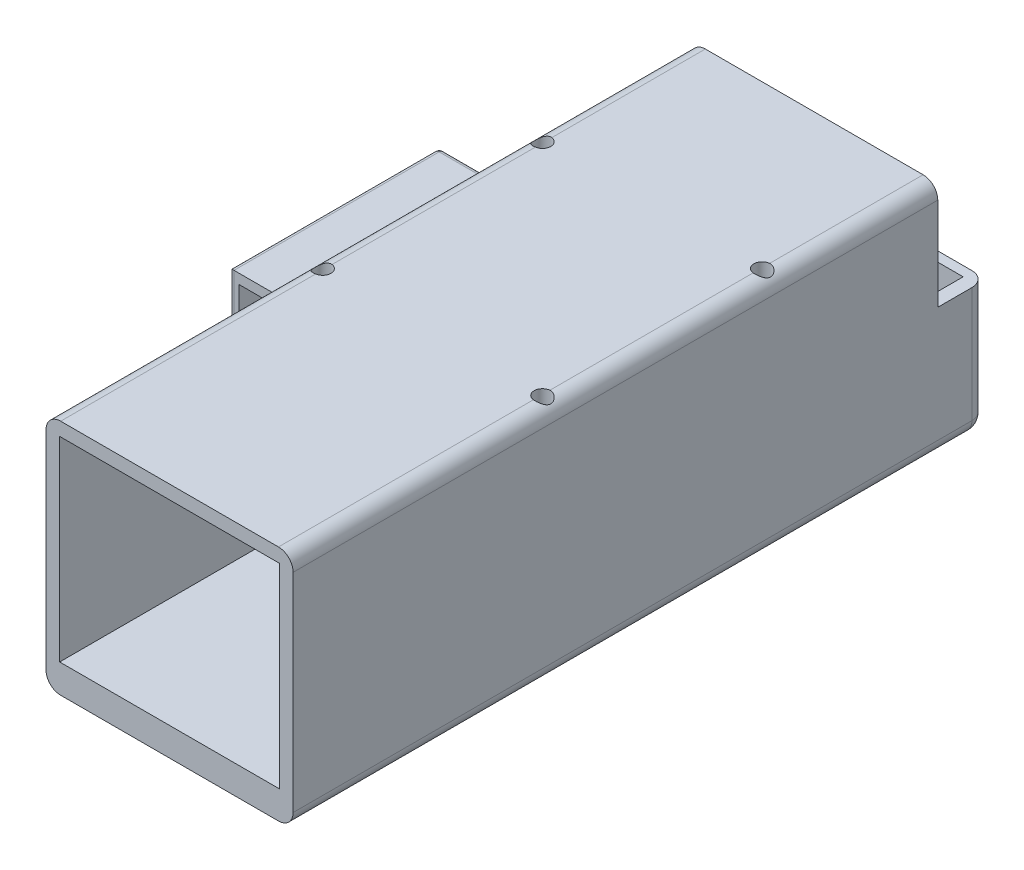
SolidWorks part; units mm, degrees
material "ABS"
ref_plane "Front Plane" through (0, 0, 0) normal (0, 0, 1) x (1, 0, 0)
ref_plane "Top Plane" through (0, 0, 0) normal (0, 1, 0) x (1, 0, 0)
ref_plane "Right Plane" through (0, 0, 0) normal (1, 0, 0) x (0, 0, -1)
sketch "Sketch1" plane through (0, 0, 0) normal (0, 0, 1) x (1, 0, 0)
  line L0 (-22.5, 20) -> (22.5, -20) construction
  line L1 (-22.5, 20) -> (22.5, 20)
  line L2 (-22.5, 20) -> (-22.5, -20)
  line L3 (-22.5, -20) -> (22.5, -20)
  line L4 (22.5, 20) -> (22.5, -20)
  line L5 (-25.3, 22.8) -> (-25.3, -22.8)
  line L6 (-25.3, -22.8) -> (25.3, -22.8)
  line L7 (25.3, 22.8) -> (25.3, -22.8)
  line L8 (-25.3, 22.8) -> (25.3, 22.8)
  point P4 (0, 0)
  dimension "D1" = 45
  dimension "D2" = 40
  dimension "D3" = 2.8
extrude "Boss-Extrude1" add sketch "Sketch1" along normal mid plane 140
sketch "Sketch2" plane through (0, 0, -70) normal (0, 0, -1) x (-1, 0, 0)
  line L1 (-25.3, 22.8) -> (25.3, 22.8)
  line L2 (-25.3, 22.8) -> (-25.3, -22.8)
  line L3 (-25.3, -22.8) -> (25.3, -22.8)
  line L4 (25.3, 22.8) -> (25.3, -22.8)
extrude "Boss-Extrude2" add sketch "Sketch2" along normal blind 2
sketch "Sketch4" plane through (0, 22.8, 0) normal (0, 1, 0) x (1, 0, 0)
  circle A0 centre (-22.5344, 28.8905) radius 1.7
  circle A1 centre (22.4656, 28.8905) radius 1.7
  circle A2 centre (22.4656, -16.1095) radius 1.7
  circle A3 centre (-22.5344, -16.1095) radius 1.7
  dimension "D1" = 3.4
  dimension "D2" = 3.4
  dimension "D3" = 3.4
  dimension "D4" = 3.4
extrude "Cut-Extrude1" cut sketch "Sketch4" against normal blind 71.5
ref_plane "Plane1" through (0, -10, 0) normal (0, 1, 0) x (1, 0, 0)
sketch "Sketch5" plane through (0, -10, 0) normal (0, 1, 0) x (1, 0, 0)
  circle A0 centre (22.4656, 28.8905) radius 2.75
  circle A1 centre (22.4656, -16.1095) radius 2.75
  circle A2 centre (-22.5344, 28.8905) radius 2.75
  circle A3 centre (-22.5344, -16.1095) radius 2.75
  dimension "D1" = 5.5
extrude "Cut-Extrude2" cut sketch "Sketch5" against normal blind 12.5
sketch "Sketch6" plane through (0, 0, 70) normal (0, 0, 1) x (1, 0, 0)
  line L10 (-25.3, -25.8) -> (25.3, -25.8)
  line L11 (25.3, -25.8) -> (25.3, -21.5065)
  line L12 (25.3, -22.8) -> (25.3, 22.8) construction
  line L13 (25.3, -21.5065) -> (-25.3, -21.5065)
  line L14 (-25.3, 22.8) -> (-25.3, -22.8) construction
  line L15 (-25.3, -21.5065) -> (-25.3, -25.8)
extrude "Boss-Extrude3" add sketch "Sketch6" against normal up to surface (142 mm away) up to face at (0, 0, -72)
sketch "Sketch7" plane through (0, -21.5065, 0) normal (0, 1, 0) x (1, 0, 0)
  circle A0 centre (-22.5344, 28.8905) radius 1.7
  circle A1 centre (22.4656, 28.8905) radius 1.7
  circle A2 centre (22.4656, -16.1095) radius 1.7
  circle A3 centre (-22.5344, -16.1095) radius 1.7
extrude "Cut-Extrude3" cut sketch "Sketch7" against normal blind 7.5
fillet "Fillet1" radius 3 8 edges at (0, -25.8, -72) (25.3, -1.5, -72) (-25.3, -1.5, -72) (0, 22.8, -72) (25.3, -25.8, -1) (-25.3, -25.8, -1) (25.3, 22.8, -1) (-25.3, 22.8, -1)
sketch "Sketch8" plane through (0, 22.8, 0) normal (0, -1, 0) x (1, 0, 0)
  line L0 (-22.3, -72) -> (-34.1108, -72) construction
  line L1 (-34.1108, -72) -> (-34.1108, -62) construction
  line L2 (-25.3, -62) -> (25.3, -62)
  line L3 (-25.3, -69) -> (-25.3, 70) construction
  line L4 (25.3, 70) -> (25.3, -69) construction
  line L5 (25.3, -62) -> (25.3, -72)
  line L6 (25.3, -72) -> (25.3, -74.9895)
  line L7 (25.3, -74.9895) -> (-25.3, -74.9895)
  line L8 (-25.3, -74.9895) -> (-25.3, -62)
  dimension "D1" = 10
extrude "Cut-Extrude4" cut sketch "Sketch8" along normal blind 22
sketch "Sketch9" plane through (-25.3, 0, 0) normal (-1, 0, 0) x (0, 0, 1)
  line L1 (-25, 11.3) -> (16, 11.3)
  line L2 (-25, 11.3) -> (-25, -13.4)
  line L3 (-25, -13.4) -> (16, -13.4)
  line L5 (-27.2067, 22.8) -> (14.4258, 22.8) construction
  line L6 (-27, 13.3) -> (-27, -15.4)
  line L7 (-27, -15.4) -> (16, -15.4)
  line L9 (-27, 13.3) -> (16, 13.3)
  line L10 (16, 13.3) -> (16, 11.3)
  line L11 (-27, 13.3) -> (18, 13.3) construction
  line L12 (18, 13.3) -> (18, -15.4) construction
  line L13 (-27, -15.4) -> (18, -15.4) construction
  line L14 (16, 11.3) -> (16, -13.4) construction
  line L15 (16, -13.4) -> (16, -15.4)
  dimension "D1" = 41
  dimension "D2" = 24.7
  dimension "D4" = 11.5
  dimension "D5" = 2
extrude "Boss-Extrude4" add sketch "Sketch9" along normal blind 14.5
sketch "Sketch10" plane through (-39.8, 0, 0) normal (-1, 0, 0) x (0, 0, 1)
  line L1 (-27, 13.3) -> (16, 13.3)
  line L2 (-27, 13.3) -> (-27, -15.4)
  line L3 (-27, -15.4) -> (16, -15.4)
  line L4 (16, 13.3) -> (16, -15.4)
extrude "Boss-Extrude5" add sketch "Sketch10" along normal blind 2
sketch "Sketch11" plane through (-41.8, 0, 0) normal (-1, 0, 0) x (0, 0, 1)
  line L0 (16, -1.05) -> (4, -1.05) construction
  line L1 (16, -15.4) -> (16, 13.3) construction
  line L2 (4, 11.3) -> (4, -13.4)
  line L6 (-10, -13.4) -> (-10, 11.3)
  line L9 (-10, 11.3) -> (4, 11.3)
  line L10 (-10, -13.4) -> (4, -13.4)
  dimension "D1" = 12
  dimension "D2" = 14
extrude "Cut-Extrude5" cut sketch "Sketch11" against normal blind 2
sketch "Sketch12" plane through (0, 0, -27) normal (0, 0, -1) x (-1, 0, 0)
  line L0 (33.55, 13.3) -> (33.55, -1.05) construction
  line L1 (41.8, 13.3) -> (25.3, 13.3) construction
  line L3 (33.55, -1.05) -> (41.8, -1.05) construction
  line L4 (41.8, 13.3) -> (41.8, -15.4) construction
  line L5 (33.55, -1.05) -> (33.55, -15.4) construction
  line L6 (41.8, -15.4) -> (25.3, -15.4) construction
  line L8 (30.55, 9.125) -> (36.55, 9.125)
  line L9 (30.55, 9.125) -> (30.55, 3.125)
  line L10 (30.55, 3.125) -> (36.55, 3.125)
  line L11 (36.55, 9.125) -> (36.55, 3.125)
  line L12 (30.55, 9.125) -> (36.55, 3.125) construction
  line L13 (30.55, 3.125) -> (36.55, 9.125) construction
  line L14 (30.55, -5.225) -> (36.55, -5.225)
  line L15 (30.55, -5.225) -> (30.55, -11.225)
  line L16 (30.55, -11.225) -> (36.55, -11.225)
  line L17 (36.55, -5.225) -> (36.55, -11.225)
  line L18 (30.55, -5.225) -> (36.55, -11.225) construction
  line L19 (30.55, -11.225) -> (36.55, -5.225) construction
  point P1 (33.55, 6.125)
  point P15 (33.55, -8.225)
  dimension "D1" = 6
  dimension "D2" = 6
  dimension "D3" = 6
  dimension "D4" = 6
extrude "Cut-Extrude6" cut sketch "Sketch12" against normal blind 2
fillet "Fillet2" radius 1 6 edges at (-41.8, -1.05, 16) (-41.8, -15.4, -5.5) (-33.55, -15.4, -27) (-41.8, -1.05, -27) (-41.8, 13.3, -5.5) (-33.55, 13.3, -27)
